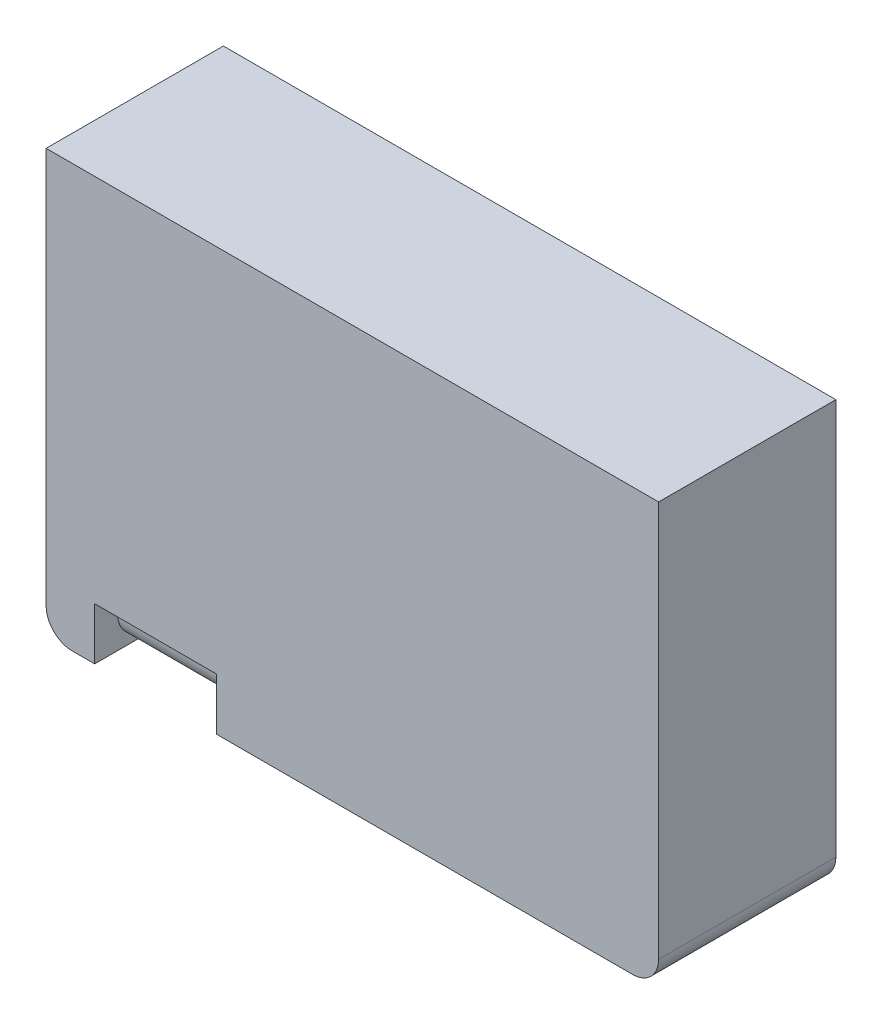
SolidWorks part; units mm, degrees
ref_plane "Front Plane" through (0, 0, 0) normal (0, 0, 1) x (1, 0, 0)
ref_plane "Top Plane" through (0, 0, 0) normal (0, 1, 0) x (1, 0, 0)
ref_plane "Right Plane" through (0, 0, 0) normal (1, 0, 0) x (0, 0, -1)
sketch "Sketch1" plane through (0, 0, 0) normal (0, 0, 1) x (1, 0, 0)
  line L1 (-26.7571, 22.6014) -> (-3.2571, 22.6014)
  line L2 (-26.7571, 22.6014) -> (-26.7571, 6.4014)
  line L3 (-26.7571, 6.4014) -> (-3.2571, 6.4014)
  line L4 (-3.2571, 22.6014) -> (-3.2571, 6.4014)
  dimension "D1" = 23.5
  dimension "D2" = 16.2
extrude "Boss-Extrude1" add sketch "Sketch1" along normal blind 6.8
fillet "Fillet1" radius 1 2 edges at (-3.2571, 6.4014, 3.4) (-26.7571, 6.4014, 3.4)
sketch "Sketch2" plane through (0, 6.4014, 0) normal (0, -1, 0) x (1, 0, 0)
  line L1 (-11.184, 5.8525) -> (-4.6184, 5.8525)
  line L2 (-11.184, 5.8525) -> (-11.184, 1.3794)
  line L3 (-11.184, 1.3794) -> (-4.6184, 1.3794)
  line L4 (-4.6184, 5.8525) -> (-4.6184, 1.3794)
  line L5 (-20.2221, 7.3962) -> (-24.8935, 7.3962)
  line L6 (-20.2221, 7.3962) -> (-20.2221, 1.3269)
  line L7 (-20.2221, 1.3269) -> (-24.8935, 1.3269)
  line L8 (-24.8935, 7.3962) -> (-24.8935, 1.3269)
  circle A0 centre (-15.9886, 3.5159) radius 2.2366
extrude "Cut-Extrude1" cut sketch "Sketch2" against normal blind 2
sketch "Sketch3" plane through (0, 8.4014, 0) normal (0, -1, 0) x (-1, 0, 0)
  line L0 (20.2221, -1.3269) -> (20.2221, -6.8) construction
  line L1 (20.2221, -5.9172) -> (24.8935, -5.9172)
  line L2 (20.2221, -5.9172) -> (20.2221, -1.6753)
  line L3 (20.2221, -1.6753) -> (24.8935, -1.6753)
  line L4 (24.8935, -5.9172) -> (24.8935, -1.6753)
  line L5 (24.8935, -6.8) -> (24.8935, -1.3269) construction
  line L6 (11.184, -5.8525) -> (11.184, -1.3794) construction
  line L7 (11.184, -5.6873) -> (4.6184, -5.6873)
  line L8 (11.184, -5.6873) -> (11.184, -1.6024)
  line L9 (11.184, -1.6024) -> (4.6184, -1.6024)
  line L10 (4.6184, -5.6873) -> (4.6184, -1.6024)
  line L11 (4.6184, -1.3794) -> (4.6184, -5.8525) construction
extrude "Boss-Extrude2" add sketch "Sketch3" along normal blind 1.8
fillet "Fillet2" radius 1 2 edges at (-22.5578, 6.6014, 1.6753) (-22.5578, 6.6014, 5.9172)
fillet "Fillet3" radius 2 2 edges at (-7.9012, 6.6014, 5.6873) (-7.9012, 6.6014, 1.6024)
sketch "Sketch4" plane through (0, 8.4014, 0) normal (0, -1, 0) x (-1, 0, 0)
  circle A0 centre (16.0073, -3.4946) radius 2.0141
extrude "Boss-Extrude3" add sketch "Sketch4" along normal blind 1.8
